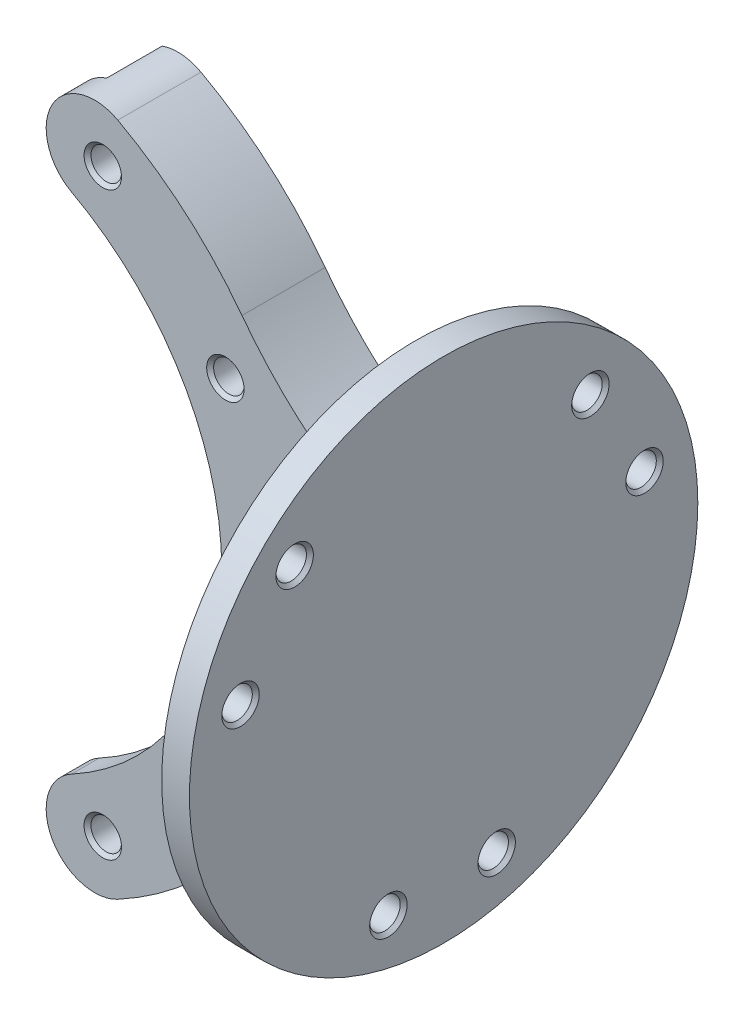
SolidWorks part; units mm, degrees
note: The reader was unsure of these and kept them because the rebuilt part matched: shared geometry of "Sketch1<7>".
ref_plane "Front Plane" through (0, 0, 0) normal (0, 0, 1) x (1, 0, 0)
ref_plane "Top Plane" through (0, 0, 0) normal (0, 1, 0) x (1, 0, 0)
ref_plane "Right Plane" through (0, 0, 0) normal (1, 0, 0) x (0, 0, -1)
sketch "Sketch1" plane through (0, 0, 0) normal (0, 0, 1) x (1, 0, 0)
  line L0 (-1000, 0) -> (49000, 0) construction
  line L1 (0, -1000) -> (0, 49000) construction
  arc A19 (14.7536, -27.2641) -> (19.7507, -36.4987) centre (17.2522, -31.8814) ccw
  arc A20 (14.7536, 27.2641) -> (19.7507, 36.4987) centre (17.2522, 31.8814) cw
  circle A21 centre (36.25, 0) radius 2
  circle A22 centre (31.3934, -18.125) radius 2
  circle A23 centre (18.125, -31.3934) radius 2
  circle A24 centre (0, -36.25) radius 2
  circle A25 centre (-18.125, -31.3934) radius 2
  circle A26 centre (-31.3934, -18.125) radius 2
  circle A27 centre (-36.25, 0) radius 2
  circle A28 centre (0, 0) radius 41.5
  circle A29 centre (0, 0) radius 40
  circle A30 centre (0, 0) radius 36.25 construction
  circle A31 centre (0, 0) radius 30 construction
  circle A32 centre (0, 0) radius 31
  circle A33 centre (-31.3934, 18.125) radius 2
  circle A34 centre (-18.125, 31.3934) radius 2
  circle A35 centre (0, 36.25) radius 2
  circle A36 centre (18.125, 31.3934) radius 2
  circle A37 centre (31.3934, 18.125) radius 2
  point P20 (0, 0)
  point P21 (36.25, 0)
  point P43 (0, 0)
  point P44 (0, 0)
  point P45 (0, 0)
  dimension "D1" = 83
  dimension "D2" = 80
  dimension "D3" = 72.5
  dimension "D4" = 60
  dimension "D7" = 31.3934
  dimension "D8" = 18.125
  dimension "D5" = 62
  dimension "D6" = 4
  dimension "D9" = 12
  dimension "D10" = 1
  dimension "D11" = 1
extrude "Boss-Extrude5" add sketch "Sketch1" along normal blind 3 contours A32 A19 A29 A20 A37 A36 A21 A22 A23 | A29 A19 A28 A20 | A36 | A37 | A21 | A22 | A23
extrude "Boss-Extrude6" add sketch "Sketch1<7>" against normal blind 6 contours A29 A19 A28 A20
sketch "Sketch1<7>" plane through (0, 0, 0) normal (0, 0, 1) x (1, 0, 0) same geometry as "Sketch1"
sketch "Sketch21" plane through (0, 0, 3) normal (0, 0, 1) x (1, 0, 0)
  line L0 (-1000, 0) -> (49000, 0) construction
  circle A0 centre (0, 0) radius 36.25 construction
  point P3 (36.25, 0)
  point P5 (0, 0)
  point P7 (0, 0)
  dimension "D1" = 72.5
hole_wizard "M4x0.7 Tapped Hole4" positions "Sketch22" profile "Sketch23" tap size "M4x0.7" standard "ANSI Metric"
sketch "Sketch22" plane through (0, 0, 3) normal (0, 0, 1) x (1, 0, 0)
  point P0 (36.25, 0)
sketch "Sketch23" plane through (36.25, 0, 3) normal (1, 0, 0) x (0, -1, 0)
  line L0 (0, 0) -> (0, 11.0914)
  line L1 (0, 11.0914) -> (1.65, 10.1)
  line L2 (1.65, 10.1) -> (1.65, 0.375)
  line L3 (1.65, 0.375) -> (2.025, 0)
  line L5 (2.025, 0) -> (0, 0)
  line L6 (-1.65, 0.375) -> (-2.025, 0) construction
  line L10 (0, 11.0914) -> (-1.65, 10.1) construction
  line L11 (0, -6.35) -> (0, 107.95) construction
  dimension "Tap Drill Dia." = 3.3
  dimension "Tap Drill Depth" = 10.1
  dimension "Near C'Sink Dia." = 4.05
  dimension "Near C'Sink Angle" = 90
  dimension "Drill Angle" = 118
cosmetic thread "Hole Thread4" parameters "D1"=8, "D2"=4
sketch "Sketch24" plane through (0, 0, 0) normal (1, 0, 0) x (0, 0, -1)
  line L0 (-1000, 0) -> (49000, 0) construction
pattern_circular "CirPattern4" count 12 over 360 about axis through (0, 0, 0) along (0, 0, 1) of "M4x0.7 Tapped Hole4"
sketch "Sketch15" plane through (0, 0, 3) normal (0, 0, 1) x (1, 0, 0)
  line L0 (-1000, 0) -> (49000, 0) construction
  line L1 (0, -1000) -> (0, 49000) construction
  line L2 (47.5, -1000) -> (47.5, 49000) construction
  line L3 (-1000, 12.5) -> (49000, 12.5) construction
  line L4 (-1000, -12.5) -> (49000, -12.5) construction
  line L5 (47.5, 12.5) -> (47.5, -12.5)
  arc A0 (33.1864, 24.9181) -> (47.5, 12.5) centre (69.1716, 51.9378) ccw
  arc A1 (19.7507, -36.4987) -> (19.7507, 36.4987) centre (0, 0) ccw construction
  arc A2 (33.1864, -24.9181) -> (47.5, -12.5) centre (69.1716, -51.9378) cw
  arc A7 (14.7536, -27.2641) -> (14.7536, 27.2641) centre (0, 0) ccw
  arc A8 (14.7536, -27.2641) -> (19.7507, -36.4987) centre (17.2522, -31.8814) ccw
  arc A9 (19.7507, -36.4987) -> (19.7507, 36.4987) centre (0, 0) ccw
  arc A10 (19.7507, 36.4987) -> (14.7536, 27.2641) centre (17.2522, 31.8814) ccw
  arc A13 (33.1864, -24.9181) -> (33.1864, 24.9181) centre (0, 0) ccw
  dimension "D5" = 45
  dimension "D6" = 45
  dimension "D1" = 47.5
  dimension "D2" = 12.5
  dimension "D3" = 25
  dimension "D4" = 0
extrude "Boss-Extrude8" add sketch "Sketch15" against normal blind 9
sketch "Sketch25" plane through (47.5, 0, 0) normal (1, 0, 0) x (0, 0, -1)
  line L0 (-1000, 0) -> (49000, 0) construction
  line L1 (1.5, -1000) -> (1.5, 49000) construction
  line L4 (-3, 12.5) -> (-3, -12.5)
  line L5 (-3, -12.5) -> (6, -12.5)
  line L6 (6, -12.5) -> (6, 12.5)
  line L7 (6, 12.5) -> (-3, 12.5)
  line L8 (-3, 12.5) -> (-3, -12.5)
  line L9 (-3, -12.5) -> (6, -12.5)
  line L10 (6, -12.5) -> (6, 12.5)
  line L11 (6, 12.5) -> (-3, 12.5)
  circle A0 centre (1.5, 0) radius 27.5
  line M6 (-3, 12.5) -> (-3, -12.5)
  line M7 (-3, -12.5) -> (6, -12.5)
  line M8 (6, -12.5) -> (6, 12.5)
  line M9 (6, 12.5) -> (-3, 12.5)
  dimension "D3" = 55
  dimension "D2" = 4.5
  dimension "D1" = 0
extrude "Boss-Extrude9" add sketch "Sketch25" along normal blind 3 contours M9 M6 M7 M8 | A0 M6 M9 M8 M7
sketch "Sketch26" plane through (50.5, 0, 0) normal (1, 0, 0) x (0, 0, -1)
  line L0 (-998.5, 0) -> (49001.5, 0) construction
  line L1 (1.5, -1000) -> (1.5, 49000) construction
  line L2 (1.5, 0) -> (23.2333, 5.8234) construction
  circle A0 centre (1.5, 0) radius 22.5 construction
  circle A1 centre (1.5, 0) radius 27.5
  circle A2 centre (1.5, 0) radius 27.5
  point P10 (23.2333, 5.8234)
  dimension "D2" = 45
  dimension "D3" = 15
  dimension "D1" = 0
hole_wizard "M4x0.7 Tapped Hole5" positions "Sketch27" profile "Sketch28" tap size "M4x0.7" standard "ANSI Metric"
sketch "Sketch27" plane through (50.5, 0, 0) normal (1, 0, 0) x (0, 0, -1)
  point P0 (23.2333, 5.8234)
sketch "Sketch28" plane through (50.5, 5.8234, -23.2333) normal (0, 1, 0) x (0, 0, -1)
  line L0 (0, 0) -> (0, 11.0914)
  line L1 (0, 11.0914) -> (1.65, 10.1)
  line L2 (1.65, 10.1) -> (1.65, 0.375)
  line L3 (1.65, 0.375) -> (2.025, 0)
  line L5 (2.025, 0) -> (0, 0)
  line L6 (-1.65, 0.375) -> (-2.025, 0) construction
  line L10 (0, 11.0914) -> (-1.65, 10.1) construction
  line L11 (0, -6.35) -> (0, 107.95) construction
  dimension "Tap Drill Dia." = 3.3
  dimension "Tap Drill Depth" = 10.1
  dimension "Near C'Sink Dia." = 4.05
  dimension "Near C'Sink Angle" = 90
  dimension "Drill Angle" = 118
cosmetic thread "Hole Thread5" parameters "D1"=8, "D2"=4
pattern_circular "CirPattern5" count 12 over 360 about axis through (0, -0.0317, -1.3815) along (1, 0, 0) skipping 2, 3, 6, 7, 10, 11 of "M4x0.7 Tapped Hole5"
fillet "Fillet2" radius 3 4 edges at (47.5, 0, 3) (47.5, -12.5, -1.5) (47.5, 0, -6) (47.5, 12.5, -1.5)
